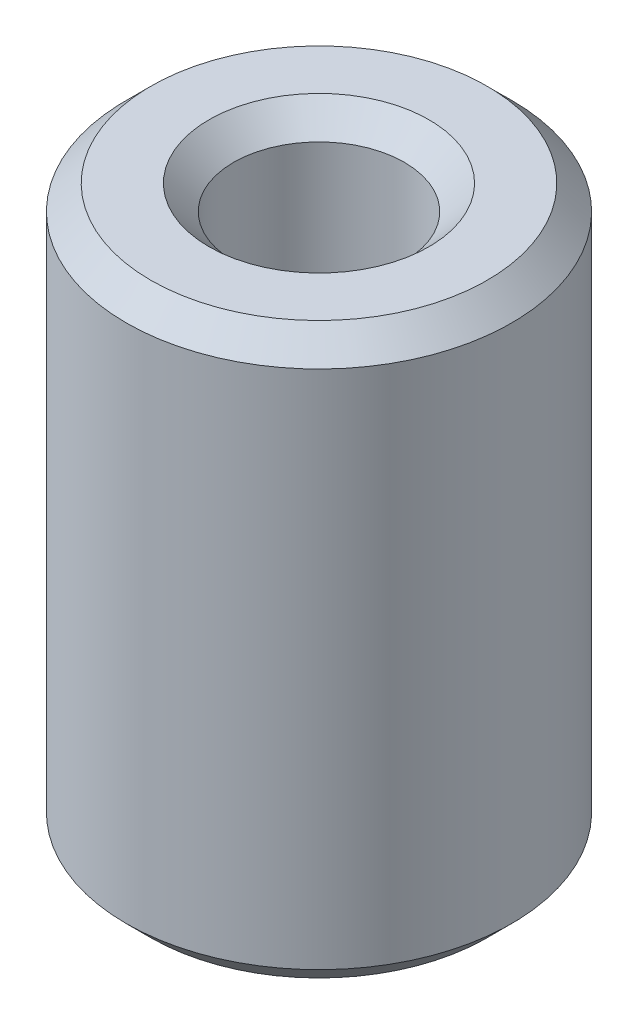
SolidWorks part; units mm, degrees
ref_plane "Front Plane" through (0, 0, 0) normal (0, 0, 1) x (1, 0, 0)
ref_plane "Top Plane" through (0, 0, 0) normal (0, 1, 0) x (1, 0, 0)
ref_plane "Right Plane" through (0, 0, 0) normal (1, 0, 0) x (0, 0, -1)
sketch "Sketch1" plane through (0, 0, 0) normal (0, 1, 0) x (1, 0, 0)
  circle A0 centre (0, 0) radius 27.5
  dimension "SLEEVE_OD" = 55
extrude "Boss-Extrude1" add sketch "Sketch1" along normal blind 81.2302
sketch "Sketch2" plane through (0, 0, 0) normal (0, 1, 0) x (1, 0, 0)
  circle A0 centre (0, 0) radius 12.1864
  dimension "BORE_D" = 24.3728
extrude "Cut-Extrude1" cut sketch "Sketch2" along normal through all
chamfer "Chamfer1" distance 3.5098 angle 45 4 edges at (0, 81.2302, 12.1864) (0, 0, 12.1864) (0, 0, 27.5) (0, 81.2302, 27.5)
